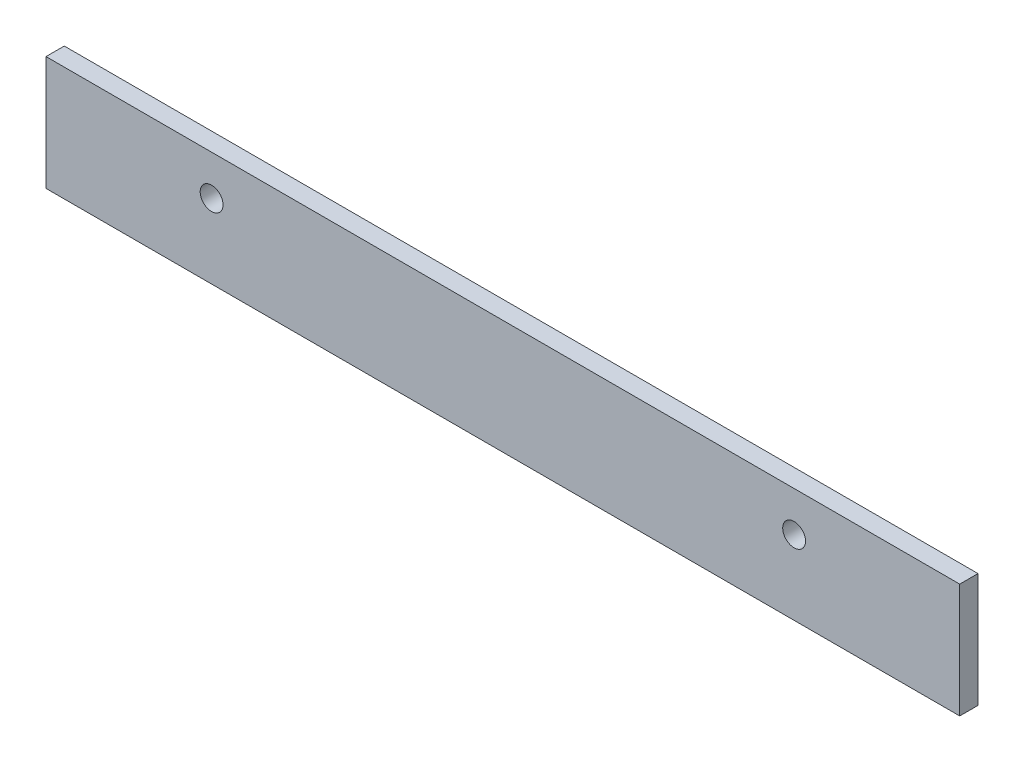
SolidWorks part; units mm, degrees
ref_plane "Front Plane" through (0, 0, 0) normal (0, 0, 1) x (1, 0, 0)
ref_plane "Top Plane" through (0, 0, 0) normal (0, 1, 0) x (1, 0, 0)
ref_plane "Right Plane" through (0, 0, 0) normal (1, 0, 0) x (0, 0, -1)
ref_plane "Plane1" through (0, 0, 10) normal (0, 0, 1) x (1, 0, 0)
sketch "Sketch2" plane through (0, -10, 10) normal (0, 0, -1) x (1, 0, 0)
  line L1 (0, -10) -> (160, -10)
  line L2 (0, -10) -> (0, 10)
  line L3 (0, 10) -> (160, 10)
  line L4 (160, -10) -> (160, 10)
  dimension "D1" = 20
  dimension "D2" = 160
extrude "Boss-Extrude1" add sketch "Sketch2" along normal blind 3.2
sketch "Sketch4" plane through (0, 0, 0) normal (0, 1, 0) x (1, 0, 0)
  line L0 (0, -10) -> (160, -10) construction
  line L1 (0, -6.8) -> (80, -6.8)
  line L2 (0, -6.8) -> (0, -10)
  line L3 (0, -10) -> (80, -10)
  line L4 (80, -6.8) -> (80, -10)
  line L5 (160, -6.8) -> (160, -10) construction
  dimension "D1" = 80
  dimension "D2" = 80
sketch "Sketch5" plane through (0, 0, 10) normal (0, 0, 1) x (1, 0, 0)
  line L0 (102, 2.15) -> (102, -20)
  line L1 (102, 0) -> (102, 4.3) construction
  line L2 (160, -20) -> (0, -20) construction
  line L3 (58, 2.15) -> (58, -20)
  line L4 (58, 0) -> (58, 4.3) construction
  line L7 (29, -7) -> (131, -7)
  line L9 (0, 0) -> (160, 0) construction
  circle A0 centre (131, -7) radius 2
  circle A1 centre (29, -7) radius 2
  dimension "D1" = 7
extrude "Cut-Extrude1" cut sketch "Sketch5" against normal through all both and the other way through all contours A0 | A1
